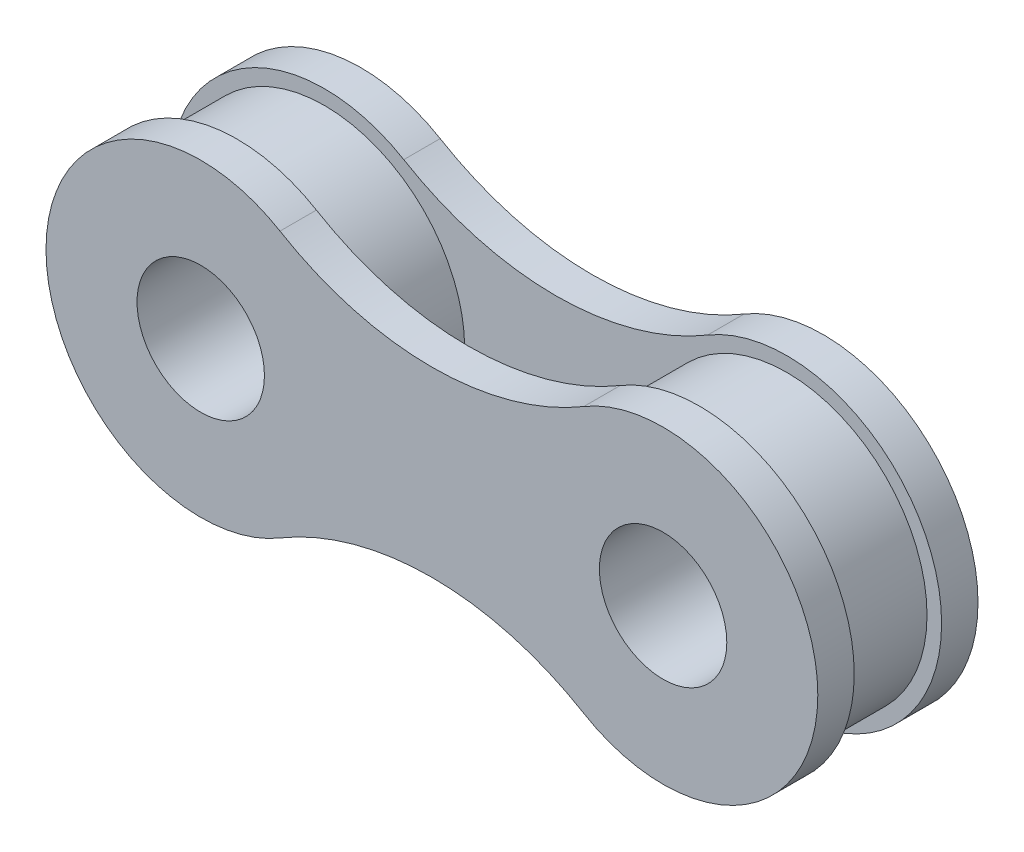
SolidWorks part; units mm, degrees
ref_plane "Front Plane" through (0, 0, 0) normal (0, 0, 1) x (1, 0, 0)
ref_plane "Top Plane" through (0, 0, 0) normal (0, 1, 0) x (1, 0, 0)
ref_plane "Right Plane" through (0, 0, 0) normal (1, 0, 0) x (0, 0, -1)
sketch "Sketch1" plane through (0, 0, 0) normal (0, 0, 1) x (1, 0, 0)
  arc A0 (2.1772, 3.65) -> (2.1772, -3.65) centre (0, 0) ccw
  arc A1 (10.5228, -3.65) -> (10.5228, 3.65) centre (12.7, 0) ccw
  arc A2 (10.5228, 3.65) -> (2.1772, 3.65) centre (6.35, 10.6457) cw
  arc A3 (10.5228, -3.65) -> (2.1772, -3.65) centre (6.35, -10.6457) ccw
  circle A4 centre (0, 0) radius 1.75
  circle A5 centre (12.7, 0) radius 1.75
  dimension "D1" = 8.5
  dimension "D2" = 12.7
  dimension "D3" = 5
  dimension "D4" = 3.5
extrude "Boss-Extrude1" add sketch "Sketch1" along normal blind 1
move or copy body "Body-Move/Copy1" bodies to move or copy 101 copy yes number of copies 1 translate (0, 0, 3.4)
sketch "Sketch4" plane through (0, 0, 1) normal (0, 0, 1) x (1, 0, 0)
  circle A0 centre (0, 0) radius 3.85
  circle A1 centre (0, 0) radius 1.75
  circle A2 centre (0, 0) radius 1.75 construction
  circle A3 centre (12.7, 0) radius 3.85
  circle A4 centre (12.7, 0) radius 1.75
  circle A5 centre (12.7, 0) radius 1.75 construction
  dimension "D1" = 7.7
extrude "Boss-Extrude3" add sketch "Sketch4" along normal up to next
ref_plane "Plane2" through (0, 0, 2.2) normal (0, 0, 1) x (1, 0, 0)
sketch "Sketch5" plane through (0, 0, 2.2) normal (0, 0, 1) x (1, 0, 0)
  point P0 (0, 0)
  point P1 (12.7, 0)
ref_axis "Axis1" through (0, 0, 4.4) along (0, 0, -1)
ref_axis "Axis2" through (12.7, 0, 4.4) along (0, 0, -1)
